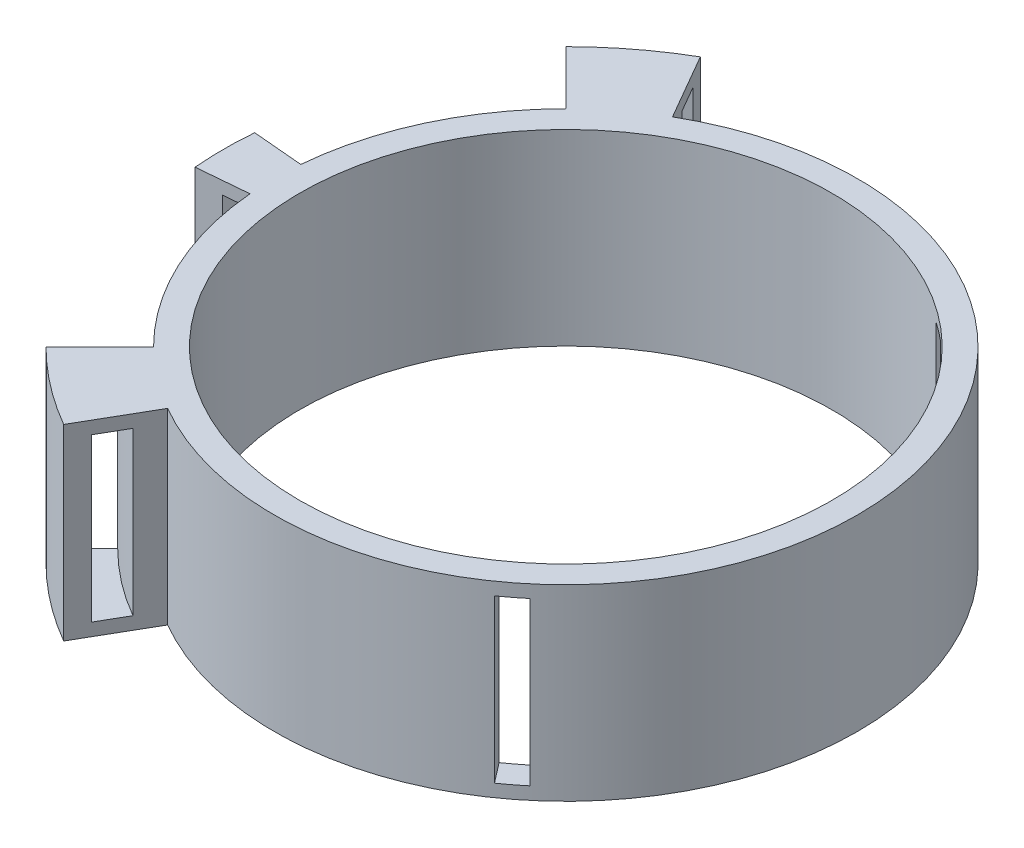
SolidWorks part; units mm, degrees
ref_plane "前视基准面" through (0, 0, 0) normal (0, 0, 1) x (1, 0, 0)
ref_plane "上视基准面" through (0, 0, 0) normal (0, 1, 0) x (1, 0, 0)
ref_plane "右视基准面" through (0, 0, 0) normal (1, 0, 0) x (0, 0, -1)
sketch "草图1" plane through (0, 0, 0) normal (0, 1, 0) x (1, 0, 0)
  line L0 (0, 0) -> (11.4562, -1.0023) construction
  line L1 (0, 0) -> (11.4562, 1.0023) construction
  line L2 (11.4562, 1.0023) -> (10.46, 0.9151)
  line L3 (11.4562, -1.0023) -> (10.46, -0.9151)
  line L5 (0, 0) -> (-5.25, -9.0933) construction
  line L6 (0, 0) -> (-7.4246, -7.4246) construction
  line L7 (0, 0) -> (-5.25, 9.0933) construction
  line L10 (0, 0) -> (-7.4246, 7.4246) construction
  line L11 (-8.1317, 8.1317) -> (-10.253, 10.253)
  line L12 (-5.75, 9.9593) -> (-7.25, 12.5574)
  line L13 (-8.1317, -8.1317) -> (-10.253, -10.253)
  line L14 (-5.75, -9.9593) -> (-7.25, -12.5574)
  line L15 (0, 0) -> (-14.5, 0) construction
  line L16 (0, 0) -> (-10.46, 0.9151) construction
  line L17 (0, 0) -> (-10.46, -0.9151) construction
  line L18 (-11.4562, 1.0023) -> (-13.4486, 1.1766)
  line L19 (-11.4562, -1.0023) -> (-13.4486, -1.1766)
  arc A0 (10.46, 0.9151) -> (10.46, -0.9151) centre (0, 0) ccw
  arc A1 (11.4562, 1.0023) -> (-5.75, 9.9593) centre (0, 0) ccw
  arc A2 (-7.25, 12.5574) -> (-10.253, 10.253) centre (0, 0) ccw
  arc A3 (-10.253, -10.253) -> (-7.25, -12.5574) centre (0, 0) ccw
  arc A4 (-8.1317, 8.1317) -> (-11.4562, 1.0023) centre (0, 0) ccw
  arc A5 (-5.75, -9.9593) -> (11.4562, -1.0023) centre (0, 0) ccw
  arc A6 (-13.4486, 1.1766) -> (-13.4486, -1.1766) centre (0, 0) ccw
  arc A7 (-11.4562, -1.0023) -> (-8.1317, -8.1317) centre (0, 0) ccw
extrude "凸台-拉伸1" add sketch "草图1" along normal blind 0.5
sketch "草图10" plane through (0, 0.5, 0) normal (0, 1, 0) x (1, 0, 0)
  line L0 (0, 0) -> (10.46, -0.9151) construction
  line L1 (10.46, -0.9151) -> (11.4562, -1.0023)
  line L2 (10.46, 0.9151) -> (11.4562, 1.0023)
  line L3 (0, 0) -> (7.3921, -8.8095) construction
  line L4 (7.3921, -8.8095) -> (6.6015, -9.4165) construction
  line L5 (6.6015, -9.4165) -> (5.9919, -8.6225) construction
  line L6 (7.3921, -8.8095) -> (6.7493, -8.0435)
  line L7 (6.6015, -9.4165) -> (5.9919, -8.6225)
  line L8 (0, 0) -> (7.3482, 8.8461) construction
  line L9 (7.3482, 8.8461) -> (6.5537, 9.4498) construction
  line L10 (6.5537, 9.4498) -> (5.9481, 8.6528) construction
  line L11 (5.9481, 8.6528) -> (6.5537, 9.4498)
  line L12 (7.3482, 8.8461) -> (6.7092, 8.0769)
  arc A0 (10.46, 0.9151) -> (6.7092, 8.0769) centre (0, 0) ccw
  arc A1 (11.4562, 1.0023) -> (7.3482, 8.8461) centre (0, 0) ccw
  arc A2 (11.4562, 1.0023) -> (-5.75, 9.9593) centre (0, 0) ccw construction
  arc A3 (6.7493, -8.0435) -> (10.46, -0.9151) centre (0, 0) ccw
  arc A4 (7.3921, -8.8095) -> (11.4562, -1.0023) centre (0, 0) ccw
  arc A5 (5.9481, 8.6528) -> (5.9919, -8.6225) centre (0, 0) ccw
  arc A6 (6.5537, 9.4498) -> (6.6015, -9.4165) centre (0, 0) ccw
  arc M10 (11.4562, 1.0023) -> (-5.75, 9.9593) centre (0, 0) ccw
  line M11 (11.4562, -1.0023) -> (10.46, -0.9151)
  arc M12 (10.46, -0.9151) -> (10.46, 0.9151) centre (0, 0) cw
  line M13 (10.46, 0.9151) -> (11.4562, 1.0023)
extrude "凸台-拉伸2" add sketch "草图10" along normal blind 6.4 contours L6 M10 M11 M12 | L11 L7 M12 M10 | L12 M10 M12 M13 region at (6.0645, 0.5, 9.1977) region at (9.5148, 0.5, 4.9531) region at (9.4993, 0.5, -4.9751)
sketch "草图11" plane through (0, 6.9, 0) normal (0, 1, 0) x (1, 0, 0)
  line L0 (11.4562, -1.0023) -> (10.46, -0.9151) construction
  line L1 (10.46, 0.9151) -> (11.4562, 1.0023)
  line L2 (10.46, -0.9151) -> (11.4562, -1.0023)
  arc A0 (10.46, 0.9151) -> (10.46, -0.9151) centre (0, 0) ccw
  arc A1 (11.4562, 1.0023) -> (11.4562, -1.0023) centre (0, 0) ccw
  arc A2 (7.3921, -8.8095) -> (11.4562, -1.0023) centre (0, 0) ccw construction
extrude "凸台-拉伸3" add sketch "草图11" along normal blind 0.5
sketch "草图12" plane through (0, 0.5, 0) normal (0, 1, 0) x (1, 0, 0)
  line L2 (0, 0) -> (-5.4967, 0) construction
  line L3 (-8.1317, -8.1317) -> (-8.8388, -8.8388)
  line L4 (-8.1317, -8.1317) -> (-10.253, -10.253) construction
  line L5 (-5.75, -9.9593) -> (-6.25, -10.8253)
  line L6 (-7.25, -12.5574) -> (-5.75, -9.9593) construction
  line L7 (-10.253, -10.253) -> (-9.6874, -9.6874)
  line L8 (-7.25, -12.5574) -> (-6.85, -11.8645)
  line L9 (-10.253, 10.253) -> (-9.6874, 9.6874)
  line L10 (-7.25, 12.5574) -> (-6.85, 11.8645)
  line L11 (-5.75, 9.9593) -> (-6.25, 10.8253)
  line L12 (-8.1317, 8.1317) -> (-8.8388, 8.8388)
  line L15 (-11.4562, 1.0023) -> (-13.4486, 1.1766) construction
  line L17 (-13.4486, -1.1766) -> (-11.4562, -1.0023) construction
  line L19 (-13.4486, 1.1766) -> (-12.4524, 1.0894)
  line L20 (-13.4486, -1.1766) -> (-12.4524, -1.0894)
  arc A0 (-10.253, -10.253) -> (-7.25, -12.5574) centre (0, 0) ccw
  arc A1 (-8.1317, -8.1317) -> (-5.75, -9.9593) centre (0, 0) ccw
  arc A2 (-8.8388, -8.8388) -> (-6.25, -10.8253) centre (0, 0) ccw
  arc A3 (-9.6874, -9.6874) -> (-6.85, -11.8645) centre (0, 0) ccw
  arc A4 (-10.253, 10.253) -> (-7.25, 12.5574) centre (0, 0) cw
  arc A5 (-9.6874, 9.6874) -> (-6.85, 11.8645) centre (0, 0) cw
  arc A6 (-8.1317, 8.1317) -> (-5.75, 9.9593) centre (0, 0) cw
  arc A7 (-8.8388, 8.8388) -> (-6.25, 10.8253) centre (0, 0) cw
  arc A10 (-12.4524, 1.0894) -> (-12.4524, -1.0894) centre (0, 0) ccw
  arc A12 (-13.4486, -1.1766) -> (-13.4486, 1.1766) centre (0, 0) cw
extrude "凸台-拉伸4" add sketch "草图12" along normal blind 6.4
sketch "草图13" plane through (0, 6.9, 0) normal (0, 1, 0) x (1, 0, 0)
  line L0 (-8.1317, -8.1317) -> (-10.253, -10.253)
  line L1 (-7.25, -12.5574) -> (-5.75, -9.9593)
  line L2 (0, 0) -> (-3.2777, 0) construction
  line L3 (-7.25, 12.5574) -> (-5.75, 9.9593)
  line L4 (-8.1317, 8.1317) -> (-10.253, 10.253)
  line L11 (-13.4486, 1.1766) -> (-11.4562, 1.0023)
  line L12 (-12.4524, 1.0894) -> (-13.4486, 1.1766) construction
  line L13 (-13.4486, -1.1766) -> (-11.4562, -1.0023)
  line L14 (-13.4486, -1.1766) -> (-12.4524, -1.0894) construction
  arc A1 (-7.25, -12.5574) -> (-10.253, -10.253) centre (0, 0) cw
  arc A2 (-5.75, -9.9593) -> (-8.1317, -8.1317) centre (0, 0) cw
  arc A3 (-7.25, 12.5574) -> (-10.253, 10.253) centre (0, 0) ccw
  arc A4 (-5.75, 9.9593) -> (-8.1317, 8.1317) centre (0, 0) ccw
  arc A8 (-13.4486, 1.1766) -> (-13.4486, -1.1766) centre (0, 0) ccw
  arc A9 (-11.4562, 1.0023) -> (-11.4562, -1.0023) centre (0, 0) ccw
extrude "凸台-拉伸5" add sketch "草图13" along normal blind 0.5
sketch "草图14" plane through (0, 7.4, 0) normal (0, 1, 0) x (1, 0, 0)
  line L0 (10.46, 0.9151) -> (11.4562, 1.0023) construction
  line L1 (10.46, 0.9151) -> (11.4562, 1.0023)
  line L2 (10.46, -0.9151) -> (11.4562, -1.0023)
  arc A0 (10.46, -0.9151) -> (10.46, 0.9151) centre (0, 0) ccw
  arc A1 (11.4562, -1.0023) -> (11.4562, 1.0023) centre (0, 0) ccw
extrude "凸台-拉伸6" add sketch "草图14" against normal blind 7.4
